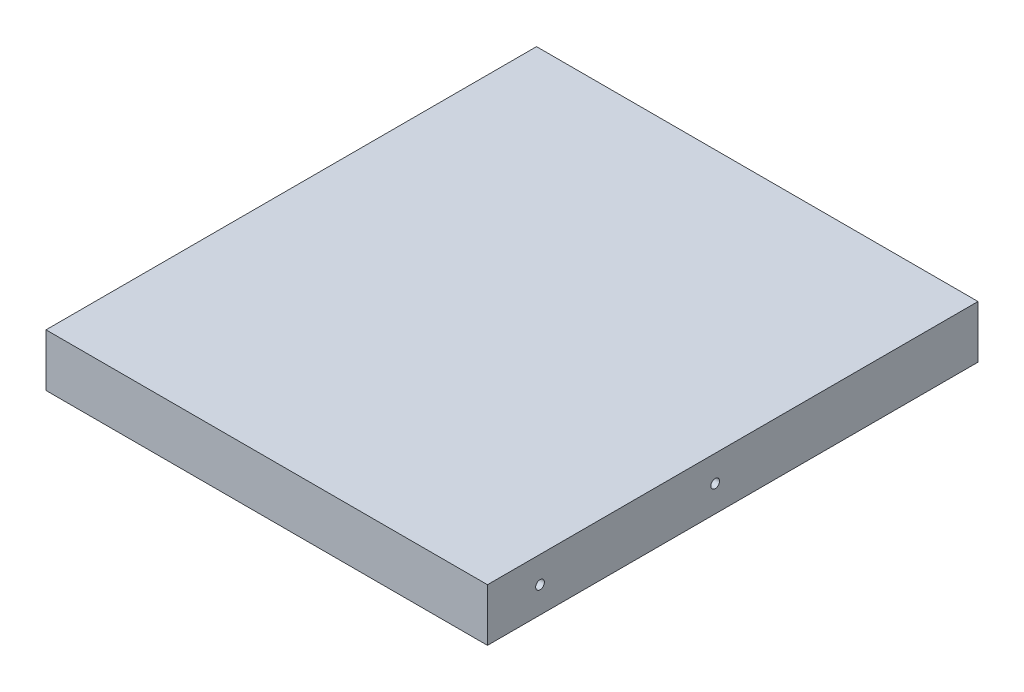
SolidWorks part; units mm, degrees
material "Beech"
ref_plane "Front Plane" through (0, 0, 0) normal (0, 0, 1) x (1, 0, 0)
ref_plane "Top Plane" through (0, 0, 0) normal (0, 1, 0) x (1, 0, 0)
ref_plane "Right Plane" through (0, 0, 0) normal (1, 0, 0) x (0, 0, -1)
sketch "Sketch1" plane through (0, 0, 0) normal (0, 0, 1) x (1, 0, 0)
  line L0 (80.01, 5194.3) -> (80.01, 5935.98) construction
  line L1 (-80.01, 5846.1044) -> (80.01, 5846.1044)
  line L2 (-80.01, 5846.1044) -> (-80.01, 5827.0544)
  line L3 (-80.01, 5827.0544) -> (80.01, 5827.0544)
  line L4 (80.01, 5846.1044) -> (80.01, 5827.0544)
  line L5 (-80.01, 5194.3) -> (-80.01, 5935.98) construction
  line L6 (-80.01, 5827.0544) -> (-99.06, 5827.0544) construction
  dimension "D1" = 19.05
extrude "Boss-Extrude1" add sketch "Sketch1" along normal offset from surface (177.8 mm away) 101.6 offset beyond the face yes
hole_wizard "Hole1" positions "Sketch2" profile "Sketch3" legacy
sketch "Sketch2" plane through (0, 0, -19.05) normal (0, 0, -1) x (-1, 0, 0)
  line L1 (0, 5194.3) -> (0, 5935.98) construction
  line L9 (80.01, 5836.5794) -> (-80.01, 5836.5794) construction
  point P1 (0.1622, 5756.275)
  point P4 (0, 5926.455)
  point P16 (-203.2, 5926.455)
  point P28 (-406.4, 5926.455)
  point P31 (-406.5622, 5756.275)
  point P43 (-203.3622, 5756.275)
  point P55 (-359.618, 5737.225)
  point P61 (-428.6139, 5737.225)
  point P64 (-421.2578, 5578.475)
  point P70 (-319.6578, 5578.475)
  point P82 (-116.4578, 5578.475)
  point P85 (-424.0726, 5559.425)
  point P91 (-358.1042, 5559.425)
  point P94 (-418.2303, 5400.675)
  point P100 (-316.6303, 5400.675)
  point P112 (-113.4303, 5400.675)
  point P115 (-419.5313, 5381.625)
  point P121 (-356.5904, 5381.625)
  point P124 (-415.2028, 5222.875)
  point P130 (-313.6028, 5222.875)
  point P144 (-110.4028, 5222.875)
  point P147 (-414.9901, 5203.825)
  point P153 (-355.0767, 5203.825)
  point P159 (355.0767, 5203.825)
  point P161 (414.9901, 5203.825)
  point P162 (110.4028, 5222.875)
  point P166 (313.6028, 5222.875)
  point P168 (415.2028, 5222.875)
  point P169 (356.5904, 5381.625)
  point P171 (419.5313, 5381.625)
  point P172 (113.4303, 5400.675)
  point P176 (316.6303, 5400.675)
  point P178 (418.2303, 5400.675)
  point P179 (358.1042, 5559.425)
  point P181 (424.0726, 5559.425)
  point P182 (116.4578, 5578.475)
  point P186 (319.6578, 5578.475)
  point P188 (421.2578, 5578.475)
  point P189 (428.6139, 5737.225)
  point P191 (359.618, 5737.225)
  point P195 (203.3622, 5756.275)
  point P199 (406.5622, 5756.275)
  point P200 (406.4, 5926.455)
  point P204 (203.2, 5926.455)
  point P208 (-0.1622, 5756.275)
  point P252 (0, 5836.5794)
  point P254 (-60.96, 5836.5794)
  point P256 (60.96, 5836.5794)
sketch "Sketch3" plane through (-0.1622, 5756.275, -19.05) normal (1, 0, 0) x (0, 1, 0)
  line L0 (0, 0) -> (0, 32.346)
  line L1 (0, 32.346) -> (0.9919, 31.75)
  line L2 (0.9919, 31.75) -> (0.9919, 4.7029)
  line L3 (0.9919, 4.7029) -> (5.08, 0)
  line L4 (5.08, 0) -> (0, 0)
  line L5 (0, -14.3089) -> (0, 102.4216) construction
  line L6 (0, 32.346) -> (-0.9919, 31.75) construction
  line L7 (-0.9919, 4.7029) -> (-5.08, 0) construction
  dimension "Diameter" = 1.9837
  dimension "Depth" = 31.75
  dimension "C-Sink Diameter" = 10.16
  dimension "C-Sink Angle" = 82
  dimension "Drill Angle" = 118
hole_wizard "Hole3" positions "Sketch6" profile "Sketch7" legacy
sketch "Sketch6" plane through (99.06, 0, -2683.51) normal (1, 0, 0) x (0, 0, -1)
  line L0 (-2759.71, 5836.5794) -> (-2861.31, 5836.5794) construction
  point P13 (-2842.26, 5836.5794)
  point P15 (-2778.76, 5836.5794)
sketch "Sketch7" plane through (99.06, 5836.5794, 95.25) normal (0, 1, 0) x (0, 0, -1)
  line L0 (0, 0) -> (0, 32.7039)
  line L1 (0, 32.7039) -> (1.5875, 31.75)
  line L2 (1.5875, 31.75) -> (1.5875, 4.0177)
  line L3 (1.5875, 4.0177) -> (5.08, 0)
  line L4 (5.08, 0) -> (0, 0)
  line L5 (0, -14.3089) -> (0, 102.4216) construction
  line L6 (0, 32.7039) -> (-1.5875, 31.75) construction
  line L7 (-1.5875, 4.0177) -> (-5.08, 0) construction
  dimension "Diameter" = 3.175
  dimension "Depth" = 31.75
  dimension "C-Sink Diameter" = 10.16
  dimension "C-Sink Angle" = 82
  dimension "Drill Angle" = 118
hole_wizard "Hole4" positions "Sketch8" profile "Sketch9" legacy
sketch "Sketch8" plane through (-99.06, 0, -2683.51) normal (-1, 0, 0) x (0, 0, 1)
  line L0 (2759.71, 5836.5794) -> (2861.31, 5836.5794) construction
  point P12 (2842.26, 5836.5794)
  point P14 (2778.76, 5836.5794)
sketch "Sketch9" plane through (-99.06, 5836.5794, 95.25) normal (0, 1, 0) x (0, 0, 1)
  line L0 (0, 0) -> (0, 32.7039)
  line L1 (0, 32.7039) -> (1.5875, 31.75)
  line L2 (1.5875, 31.75) -> (1.5875, 4.0177)
  line L3 (1.5875, 4.0177) -> (5.08, 0)
  line L4 (5.08, 0) -> (0, 0)
  line L5 (0, -14.3089) -> (0, 102.4216) construction
  line L6 (0, 32.7039) -> (-1.5875, 31.75) construction
  line L7 (-1.5875, 4.0177) -> (-5.08, 0) construction
  dimension "Diameter" = 3.175
  dimension "Depth" = 31.75
  dimension "C-Sink Diameter" = 10.16
  dimension "C-Sink Angle" = 82
  dimension "Drill Angle" = 118
